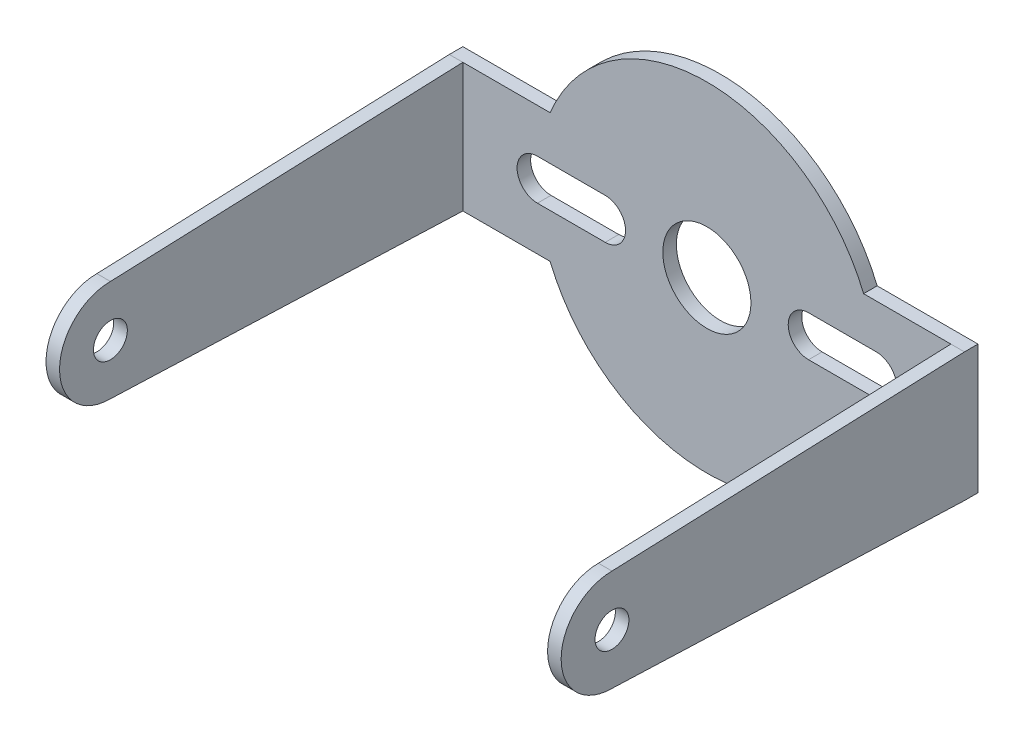
SolidWorks part; units mm, degrees
ref_plane "前视基准面" through (0, 0, 0) normal (0, 0, 1) x (1, 0, 0)
ref_plane "上视基准面" through (0, 0, 0) normal (0, 1, 0) x (1, 0, 0)
ref_plane "右视基准面" through (0, 0, 0) normal (1, 0, 0) x (0, 0, -1)
sketch "草图1" plane through (0, 0, 0) normal (0, 0, 1) x (1, 0, 0)
  line L0 (11.5623, 4.75) -> (19, 4.75)
  line L1 (-19, 4.75) -> (-11.5623, 4.75)
  line L2 (-19, 4.75) -> (-19, -4.75)
  line L3 (-19, -4.75) -> (-11.5623, -4.75)
  line L4 (19, 4.75) -> (19, -4.75)
  line L5 (-19, 4.75) -> (19, -4.75) construction
  line L6 (-19, -4.75) -> (19, 4.75) construction
  line L7 (11.5623, -4.75) -> (19, -4.75)
  arc A0 (-11.5623, -4.75) -> (11.5623, -4.75) centre (0, 0) ccw
  circle A1 centre (0, 0) radius 3.25
  arc A2 (11.5623, 4.75) -> (-11.5623, 4.75) centre (0, 0) ccw
  dimension "D3" = 25
  dimension "D4" = 6.5
  dimension "D1" = 38
  dimension "D2" = 9.5
extrude "凸台-拉伸1" add sketch "草图1" along normal blind 1
hole_wizard "Ø3.0 (3) 直径槽口1" positions "草图5" profile "草图4" size "Ø3.0" standard "GB" slot yes end condition through all
sketch "草图5" plane through (0, 0, 1) normal (0, 0, 1) x (1, 0, 0)
  line L0 (-14, 0) -> (-6, 0) construction
  point P0 (-10, 0)
  point P5 (10, 0)
  dimension "D1" = 8
  dimension "D2" = 10
  dimension "D3" = 10
sketch "草图4" plane through (-10, 0, 1) normal (1, 0, 0) x (0, -1, 0)
  line L0 (0, 0) -> (0, 1)
  line L1 (0, 1) -> (1.5, 1)
  line L2 (1.5, 1) -> (1.5, 0)
  line L5 (1.5, 0) -> (0, 0)
  line L11 (0, -6.35) -> (0, 107.95) construction
  dimension "通孔孔直径" = 3
  dimension "通孔孔深度" = 1
sketch "草图7" plane through (-19, 0, 0) normal (-1, 0, 0) x (0, 0, 1)
  line L0 (1, 4.75) -> (27, 3.75)
  line L1 (1, -4.75) -> (27, -3.75)
  line L2 (1, 4.75) -> (1, -4.75)
  arc A0 (27, -3.75) -> (27, 3.75) centre (27, 0) ccw
  circle A1 centre (27, 0) radius 1.25
  dimension "D1" = 7.5
  dimension "D3" = 2.5
  dimension "D2" = 27
extrude "凸台-拉伸2" add sketch "草图7" against normal blind 1
mirror "镜向1" about plane through (0, 0, 0) normal (1, 0, 0) of "凸台-拉伸2"
